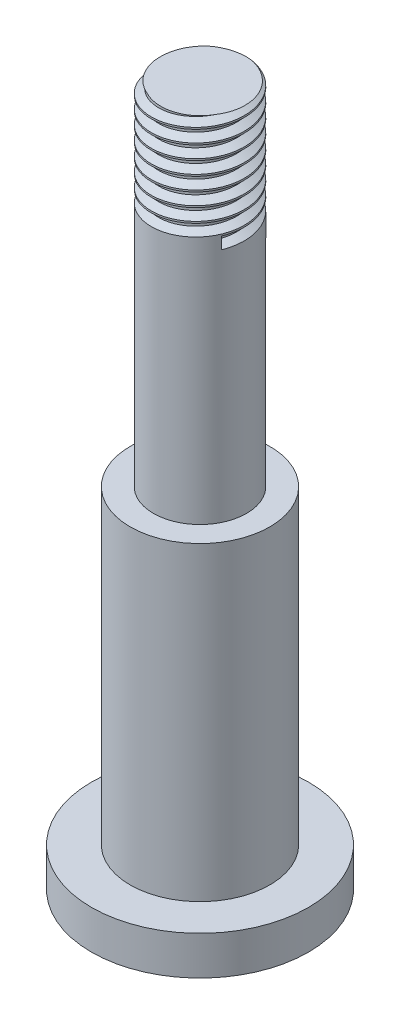
SolidWorks part; units mm, degrees
ref_plane "Front Plane" through (0, 0, 0) normal (0, 0, 1) x (1, 0, 0)
ref_plane "Top Plane" through (0, 0, 0) normal (0, 1, 0) x (1, 0, 0)
ref_plane "Right Plane" through (0, 0, 0) normal (1, 0, 0) x (0, 0, -1)
sketch "Sketch1" plane through (0, 0, 0) normal (0, 1, 0) x (1, 0, 0)
  circle A0 centre (0, 0) radius 14
extrude "Boss-Extrude1" add sketch "Sketch1" along normal blind 5
sketch "Sketch2" plane through (0, 5, 0) normal (0, 1, 0) x (1, 0, 0)
  circle A0 centre (0, 0) radius 9
extrude "Boss-Extrude2" add sketch "Sketch2" along normal blind 40
sketch "Sketch3" plane through (0, 45, 0) normal (0, 1, 0) x (1, 0, 0)
  circle A0 centre (0, 0) radius 6
extrude "Boss-Extrude3" add sketch "Sketch3" along normal blind 45
thread "Thread2" pitch 1.75 method cut profile "Thread Profile2" start angle 0, offset 2, length 15, pitch 1.75, diameter 12
ref_plane "Plane2" through (-6, 92, 0) normal (0, 0, 1) x (-1, 0, 0)
sketch "Thread Profile2" plane through (-6, 92, 0) normal (0, 0, 1) x (-1, 0, 0)
  line L0 (0, 0) -> (0, 1.75) construction
  line L11 (0, 0) -> (0, 1.5312)
  line L12 (0, 1.5312) -> (-0.9472, 0.9844)
  line L13 (-0.9472, 0.9844) -> (-0.9472, 0.5469)
  line L15 (-0.9472, 0.5469) -> (0, 0)
  line L17 (-0.9472, 0.7656) -> (0, 0.7656) construction
  point P2 (0, 0)
  dimension "Pitch" = 1.75
  dimension "Profile_Angle" = 60
  dimension "Profile_Land" = 0.4375
  dimension "Profile_Height" = 0.9472
